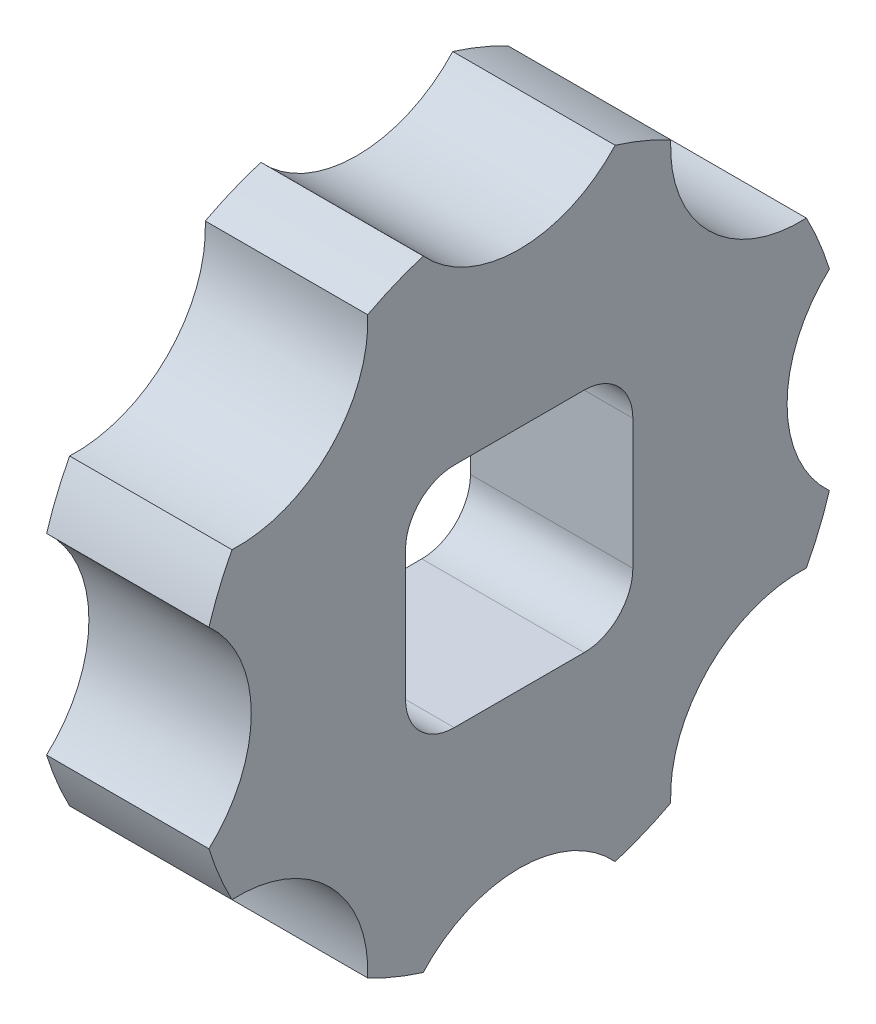
SolidWorks part; units mm, degrees
material "1345 Alloy"
ref_plane "Front Plane" through (0, 0, 0) normal (0, 0, 1) x (1, 0, 0)
ref_plane "Top Plane" through (0, 0, 0) normal (0, 1, 0) x (1, 0, 0)
ref_plane "Right Plane" through (0, 0, 0) normal (1, 0, 0) x (0, 0, -1)
other "Center of Mass"
sketch "Sketch1" plane through (0, 0, 0) normal (1, 0, 0) x (0, 0, -1)
  circle A0 centre (0, 0) radius 20
  dimension "D1" = 40
extrude "Boss-Extrude1" add sketch "Sketch1" along normal blind 10 contours A0
sketch "Sketch2" plane through (10, 0, 0) normal (1, 0, 0) x (0, 0, -1)
  line L1 (7, -7) -> (-7, -7)
  line L2 (7, -7) -> (7, 7)
  line L3 (7, 7) -> (-7, 7)
  line L4 (-7, -7) -> (-7, 7)
  line L5 (7, -7) -> (-7, 7) construction
  line L6 (7, 7) -> (-7, -7) construction
  point P0 (0, 0)
  dimension "D1" = 14
  dimension "D2" = 14
extrude "Cut-Extrude1" cut sketch "Sketch2" against normal blind 10
fillet "Fillet1" radius 3 4 edges at (5, -7, 7) (5, -7, -7) (5, 7, 7) (5, 7, -7)
sketch "Sketch3" plane through (10, 0, 0) normal (1, 0, 0) x (0, 0, -1)
  line L0 (-24.5, 0) -> (24.5, 0) construction
  circle A0 centre (24.5, 0) radius 8
  circle A2 centre (-24.5, 0) radius 8
  point P2 (0, 0)
  dimension "D1" = 16
  dimension "D2" = 49
extrude "Cut-Extrude2" cut sketch "Sketch3" against normal blind 10 contours A2
extrude "Cut-Extrude3" cut sketch "Sketch3<3>" against normal blind 10
sketch "Sketch3<3>" plane through (10, 0, 0) normal (1, 0, 0) x (0, 0, -1) same geometry as "Sketch3"
pattern_circular "CirPattern2" count 8 over 360 about axis through (10, 0, 0) along (1, 0, 0) of "Cut-Extrude2"
